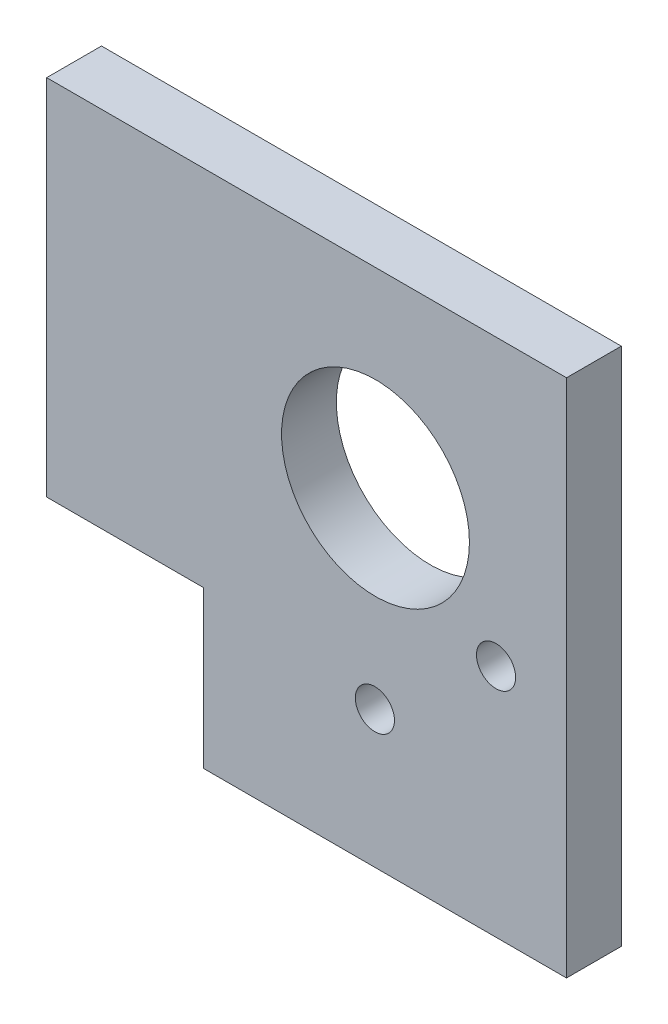
SolidWorks part; units mm, degrees
ref_plane "Front Plane" through (0, 0, 0) normal (0, 0, 1) x (1, 0, 0)
ref_plane "Top Plane" through (0, 0, 0) normal (0, 1, 0) x (1, 0, 0)
ref_plane "Right Plane" through (0, 0, 0) normal (1, 0, 0) x (0, 0, -1)
sketch "Sketch1" plane through (0, 0, 0) normal (0, 0, 1) x (1, 0, 0)
  line L0 (0, 24.4) -> (24.4, 24.4)
  line L1 (24.4, 24.4) -> (24.4, -42)
  line L2 (418, -42) -> (-22, -42) construction
  line L3 (24.4, -42) -> (-22, -42)
  line L4 (-22, -42) -> (-22, -22)
  line L5 (-22, -22) -> (-42, -22)
  line L6 (-42, -22) -> (-42, 24.4)
  line L7 (-42, -22) -> (-42, 418) construction
  line L8 (-42, 24.4) -> (0, 24.4)
  line L9 (17.0402, 21) -> (-17.0402, 21) construction
  line L10 (21, -17.0445) -> (21, 17.0402) construction
  dimension "D1" = 3.4
  dimension "D2" = 3.4
extrude "Boss-Extrude1" add sketch "Sketch1" along normal blind 7
sketch "Sketch2" plane through (0, 0, 7) normal (0, 0, 1) x (1, 0, 0)
  circle A0 centre (0, 0) radius 12
  dimension "D1" = 24
extrude "Cut-Extrude1" cut sketch "Sketch2" against normal through all
sketch "Sketch3" plane through (0, 0, 7) normal (0, 0, 1) x (1, 0, 0)
  line L0 (0, 0) -> (0, -42) construction
  line L1 (-22, -42) -> (24.4, -42) construction
  circle A1 centre (-0.076, -24.5) radius 2.5
  circle A2 centre (15.4, -12) radius 2.5
  dimension "D1" = 5
extrude "Cut-Extrude2" cut sketch "Sketch3" against normal through all
